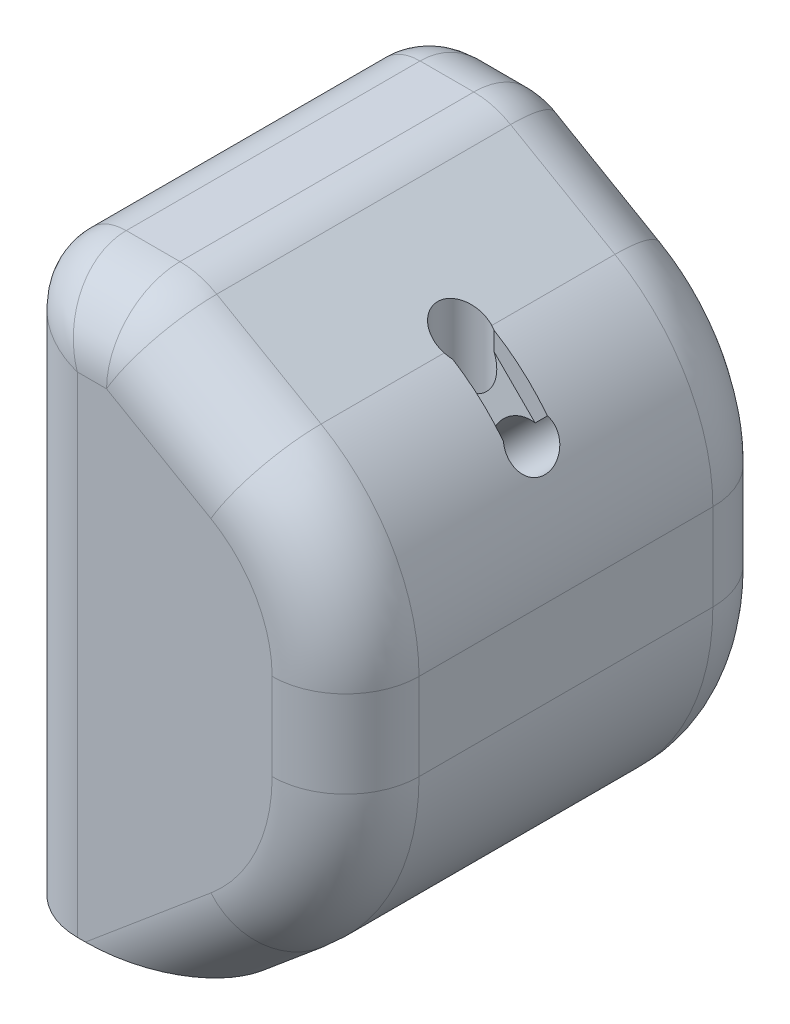
SolidWorks part; units mm, degrees
ref_plane "Front Plane" through (0, 0, 0) normal (0, 0, 1) x (1, 0, 0)
ref_plane "Top Plane" through (0, 0, 0) normal (0, 1, 0) x (1, 0, 0)
ref_plane "Right Plane" through (0, 0, 0) normal (1, 0, 0) x (0, 0, -1)
sketch "Sketch1" plane through (0, 0, 0) normal (0, 0, 1) x (1, 0, 0)
  line L0 (0, 0) -> (8, 0)
  line L1 (8, 0) -> (10.3866, 2.0026)
  line L2 (0, 0) -> (0, 21)
  line L3 (2, 23) -> (4.1962, 23)
  line L4 (5.6962, 22.5981) -> (9.9588, 20.1371)
  line L5 (13.9588, 13.2089) -> (13.9588, 9.6631)
  arc A0 (0, 21) -> (2, 23) centre (2, 21) cw
  arc A1 (5.6962, 22.5981) -> (4.1962, 23) centre (4.1962, 20) ccw
  arc A2 (13.9588, 13.2089) -> (9.9588, 20.1371) centre (5.9588, 13.2089) ccw
  arc A3 (13.9588, 9.6631) -> (10.3866, 2.0026) centre (3.9588, 9.6631) cw
  point P9 (0, 23)
  point P12 (5, 23)
  point P15 (13.9588, 17.8277)
  point P18 (13.9588, 5)
  dimension "D7" = 2
  dimension "D8" = 3
  dimension "D9" = 8
  dimension "D10" = 10
  dimension "D1" = 8
  dimension "D2" = 140
  dimension "D3" = 5
  dimension "D4" = 23
  dimension "D5" = 5
  dimension "D6" = 150
extrude "Boss-Extrude1" add sketch "Sketch1" along normal blind 18
sketch "Sketch2" plane through (0, 0, 0) normal (0, 0, -1) x (-1, 0, 0)
  line L0 (0, 0) -> (-8, 0) construction
  line L2 (-6, 0) -> (-4, 0)
  line L3 (-6, 0) -> (-6, 1.2087)
  line L5 (-4, 0) -> (-4, 1.2087)
  arc A0 (-4, 1.2087) -> (-6, 1.2087) centre (-5, 3.5) ccw
  point P0 (-5, 0)
  dimension "D2" = 5
  dimension "D1" = 5
  dimension "D3" = 3.5
  dimension "D4" = 2
  dimension "D5" = 1
extrude "Cut-Extrude1" cut sketch "Sketch2" against normal blind 12 from offset 2.5 offset against normal yes
sketch "Sketch4" plane through (0, 0, 0) normal (0, 1, 0) x (1, 0, 0)
  line L1 (8, -18) -> (8, 0) construction
  circle A0 centre (9.7202, -9) radius 1
  point P0 (8.7202, -9)
  dimension "D1" = 2
  dimension "D2" = 1
  dimension "D3" = 0.7202
  dimension "D4" = 9
extrude "Cut-Extrude3" cut sketch "Sketch4" along normal blind 25
ref_plane "Plane1" through (15.0479, 15.0479, 0) normal (0.7071, 0.7071, 0) x (0, 0, -1)
sketch "Sketch5" plane through (15.0479, 15.0479, 0) normal (0.7071, 0.7071, 0) x (0, 0, -1)
  circle A0 centre (-8.9711, 3.6971) radius 1
  point P0 (-8.9711, 7.1971)
  dimension "D1" = 2
  dimension "D2" = 3.5
  dimension "D3" = 1
extrude "Cut-Extrude4" cut sketch "Sketch5" against normal blind 4 and the other way blind 2
fillet "Fillet1" radius 3 18 edges at (9.1933, 1.0013, 0) (13.0218, 5.4369, 0) (13.9588, 11.436, 0) (12.887, 17.2089, 0) (7.8275, 21.3676, 0) (4.9726, 22.8978, 0) (3.0981, 23, 0) (0.5858, 22.4142, 0) (9.1933, 1.0013, 18) (13.0218, 5.4369, 18) (13.9588, 11.436, 18) (12.887, 17.2089, 18) (7.8275, 21.3676, 18) (4.9726, 22.8978, 18) (3.0981, 23, 18) (0.5858, 22.4142, 18) (0, 10.5, 0) (0, 10.5, 18)
sketch "Sketch6" plane through (15.0479, 15.0479, 0) normal (0.7071, 0.7071, 0) x (0, 0, -1)
  line L1 (-9.8711, 3.6971) -> (-8.0711, 3.6971)
  line L2 (-9.8711, 3.6971) -> (-9.8711, 7.4632)
  line L3 (-9.8711, 7.4632) -> (-8.0711, 7.4632)
  line L4 (-8.0711, 3.6971) -> (-8.0711, 7.4632)
  circle A0 centre (-8.9711, 3.6971) radius 1 construction
  ellipse E0 centre (-9, 7.4632) end of major axis (-9, 6.3478) minor radius 1 (-8.0289, 7.1971) -> (-9.9711, 7.1971) ccw construction
  ellipse E1 centre (-9, 7.4632) end of major axis (-9, 6.3478) minor radius 1 (-8.0289, 7.1971) -> (-9.9711, 7.1971) ccw construction
  point P5 (-9.9711, 3.6971)
  point P10 (-8.9711, 3.6971)
  dimension "D1" = 1.8
  dimension "D2" = 0.9
  dimension "D3" = 0.1289
extrude "Cut-Extrude5" cut sketch "Sketch6" along normal blind 1 and the other way blind 0.5
sketch "Sketch7" plane through (0, 0, 0) normal (-1, 0, 0) x (0, 0, 1)
  line L0 (2.9999, 14.4276) -> (3, 11)
  line L1 (3, 21) -> (3, 0) construction
  line L2 (3, 11) -> (15, 11)
  line L3 (15, 0) -> (15, 21) construction
  line L4 (15, 11) -> (15, 14.4276)
  line L5 (15, 21) -> (3, 21) construction
  spline S0 degree 3 poles (2.9999, 14.4276) (2.3845, 21.2849) (9.084, 24.4107) (15.4091, 21.3672) (15, 14.4276) knots 0 0 0 0 0.49958 1 1 1 1
  dimension "D1" = 10
extrude "Cut-Extrude6" cut sketch "Sketch7" against normal blind 0.5
ref_plane "Plane2" through (0, 0, 9) normal (0, 0, 1) x (1, 0, 0)
